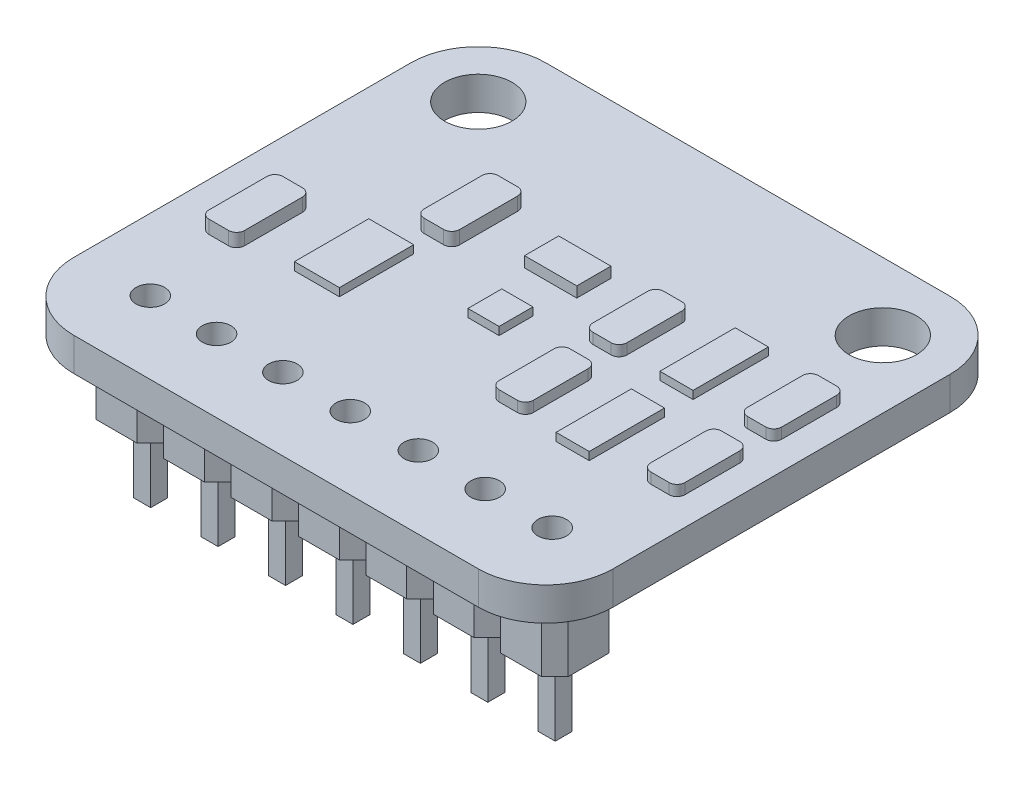
SolidWorks part; units mm, degrees
ref_plane "Front Plane" through (0, 0, 0) normal (0, 0, 1) x (1, 0, 0)
ref_plane "Top Plane" through (0, 0, 0) normal (0, 1, 0) x (1, 0, 0)
ref_plane "Right Plane" through (0, 0, 0) normal (1, 0, 0) x (0, 0, -1)
sketch "Sketch1" plane through (0, 0, 0) normal (0, 1, 0) x (1, 0, 0)
  line L0 (68.1796, -39.0616) -> (124.8504, -39.0616) construction
  line L1 (-9.3411, 12.1911) -> (5.8989, 12.1911)
  line L2 (-11.8811, 9.6511) -> (-11.8811, -3.0489)
  line L3 (-9.3411, -5.5889) -> (5.8989, -5.5889)
  line L4 (8.4389, 9.6511) -> (8.4389, -3.0489)
  line L5 (6.4112, -2.8555) -> (-9.7253, -2.8555) construction
  line L6 (-6.0638, 7.1149) -> (-5.3229, 7.1149)
  line L7 (-10.0841, 3.0308) -> (-9.3432, 3.0308)
  line L8 (-10.3841, 2.7308) -> (-10.3841, 0.547)
  line L9 (-10.0841, 0.247) -> (-9.3432, 0.247)
  line L10 (-9.0432, 2.7308) -> (-9.0432, 0.547)
  line L11 (-7.2867, 3.4702) -> (-5.5917, 3.4702)
  line L12 (-7.2867, 3.4702) -> (-7.2867, 0.6697)
  line L13 (-7.2867, 0.6697) -> (-5.5917, 0.6697)
  line L14 (-5.5917, 3.4702) -> (-5.5917, 0.6697)
  line L15 (-6.3638, 6.8149) -> (-6.3638, 4.6311)
  line L16 (-6.0638, 4.3311) -> (-5.3229, 4.3311)
  line L17 (-5.0229, 6.8149) -> (-5.0229, 4.6311)
  line L18 (6.3874, 3.0901) -> (7.0743, 3.0901)
  line L19 (-3.0469, 6.3858) -> (-1.0787, 6.3858)
  line L20 (-3.0469, 6.3858) -> (-3.0469, 5.0989)
  line L21 (-3.0469, 5.0989) -> (-1.0787, 5.0989)
  line L22 (-1.0787, 6.3858) -> (-1.0787, 5.0989)
  line L23 (0.8488, 2.9162) -> (1.5357, 2.9162)
  line L24 (0.5488, 2.6162) -> (0.5488, 0.547)
  line L25 (0.8488, 0.247) -> (1.5357, 0.247)
  line L26 (1.8357, 2.6162) -> (1.8357, 0.547)
  line L27 (6.0874, 2.7901) -> (6.0874, 0.7209)
  line L28 (6.3874, 0.4209) -> (7.0743, 0.4209)
  line L29 (7.3743, 2.7901) -> (7.3743, 0.7209)
  line L30 (6.4, 6.7237) -> (7.0869, 6.7237)
  line L31 (6.1, 6.4237) -> (6.1, 4.3544)
  line L32 (6.4, 4.0544) -> (7.0869, 4.0544)
  line L33 (7.3869, 6.4237) -> (7.3869, 4.3544)
  line L34 (0.7353, 6.5597) -> (1.4221, 6.5597)
  line L35 (0.4353, 6.2597) -> (0.4353, 4.1904)
  line L36 (0.7353, 3.8904) -> (1.4221, 3.8904)
  line L37 (1.7221, 6.2597) -> (1.7221, 4.1904)
  line L38 (3.2109, 2.8658) -> (4.4599, 2.8658)
  line L39 (3.173, 6.8149) -> (4.422, 6.8149)
  line L40 (3.173, 6.8149) -> (3.173, 3.9783)
  line L41 (3.173, 3.9783) -> (4.422, 3.9783)
  line L42 (4.422, 6.8149) -> (4.422, 3.9783)
  line L47 (-2.4918, 3.6858) -> (-1.3184, 3.6858)
  line L48 (-2.4918, 3.6858) -> (-2.4918, 2.4116)
  line L49 (-2.4918, 2.4116) -> (-1.3184, 2.4116)
  line L50 (-1.3184, 3.6858) -> (-1.3184, 2.4116)
  line L51 (3.2109, 2.8658) -> (3.2109, 0.0292)
  line L52 (3.2109, 0.0292) -> (4.4599, 0.0292)
  line L53 (4.4599, 2.8658) -> (4.4599, 0.0292)
  arc A0 (-11.8811, -3.0489) -> (-9.3411, -5.5889) centre (-9.3411, -3.0489) ccw
  arc A1 (5.8989, -5.5889) -> (8.4389, -3.0489) centre (5.8989, -3.0489) ccw
  arc A2 (5.8989, 12.1911) -> (8.4389, 9.6511) centre (5.8989, 9.6511) cw
  arc A3 (-9.3411, 12.1911) -> (-11.8811, 9.6511) centre (-9.3411, 9.6511) ccw
  circle A4 centre (-9.3411, 9.6511) radius 1.27
  circle A5 centre (5.8989, 9.6511) radius 1.27
  circle A7 centre (-6.6941, -2.8555) radius 0.54
  circle A8 centre (-4.1979, -2.8555) radius 0.54
  circle A9 centre (-1.657, -2.8555) radius 0.54
  circle A10 centre (0.9061, -2.8555) radius 0.54
  circle A11 centre (3.4246, -2.8555) radius 0.54
  circle A12 centre (5.9492, -2.8555) radius 0.54
  circle A13 centre (-9.1904, -2.8555) radius 0.54
  arc A14 (-10.3841, 0.547) -> (-10.0841, 0.247) centre (-10.0841, 0.547) ccw
  arc A15 (-9.3432, 0.247) -> (-9.0432, 0.547) centre (-9.3432, 0.547) ccw
  arc A16 (-9.3432, 3.0308) -> (-9.0432, 2.7308) centre (-9.3432, 2.7308) cw
  arc A17 (-10.0841, 3.0308) -> (-10.3841, 2.7308) centre (-10.0841, 2.7308) ccw
  arc A18 (-6.3638, 4.6311) -> (-6.0638, 4.3311) centre (-6.0638, 4.6311) ccw
  arc A19 (-5.3229, 4.3311) -> (-5.0229, 4.6311) centre (-5.3229, 4.6311) ccw
  arc A20 (-5.3229, 7.1149) -> (-5.0229, 6.8149) centre (-5.3229, 6.8149) cw
  arc A21 (-6.0638, 7.1149) -> (-6.3638, 6.8149) centre (-6.0638, 6.8149) ccw
  arc A22 (1.5357, 0.247) -> (1.8357, 0.547) centre (1.5357, 0.547) ccw
  arc A23 (0.5488, 0.547) -> (0.8488, 0.247) centre (0.8488, 0.547) ccw
  arc A24 (0.8488, 2.9162) -> (0.5488, 2.6162) centre (0.8488, 2.6162) ccw
  arc A25 (1.5357, 2.9162) -> (1.8357, 2.6162) centre (1.5357, 2.6162) cw
  arc A26 (7.0743, 0.4209) -> (7.3743, 0.7209) centre (7.0743, 0.7209) ccw
  arc A27 (6.0874, 0.7209) -> (6.3874, 0.4209) centre (6.3874, 0.7209) ccw
  arc A28 (6.3874, 3.0901) -> (6.0874, 2.7901) centre (6.3874, 2.7901) ccw
  arc A29 (7.0743, 3.0901) -> (7.3743, 2.7901) centre (7.0743, 2.7901) cw
  arc A30 (7.0869, 4.0544) -> (7.3869, 4.3544) centre (7.0869, 4.3544) ccw
  arc A31 (6.1, 4.3544) -> (6.4, 4.0544) centre (6.4, 4.3544) ccw
  arc A32 (6.4, 6.7237) -> (6.1, 6.4237) centre (6.4, 6.4237) ccw
  arc A33 (7.0869, 6.7237) -> (7.3869, 6.4237) centre (7.0869, 6.4237) cw
  arc A34 (1.4221, 3.8904) -> (1.7221, 4.1904) centre (1.4221, 4.1904) ccw
  arc A35 (0.4353, 4.1904) -> (0.7353, 3.8904) centre (0.7353, 4.1904) ccw
  arc A36 (0.7353, 6.5597) -> (0.4353, 6.2597) centre (0.7353, 6.2597) ccw
  arc A37 (1.4221, 6.5597) -> (1.7221, 6.2597) centre (1.4221, 6.2597) cw
  point P8 (-11.8811, -5.5889)
  point P11 (8.4389, -5.5889)
  point P16 (-11.8811, 12.1911)
  point P127 (0, 0)
  point P128 (0, 0)
  point P129 (0, 0)
  dimension "D3" = 2.54
  dimension "D4" = 2.54
  dimension "D5" = 2.54
  dimension "D6" = 1.08
  dimension "D7" = 0.3
  dimension "D8" = 0.3
  dimension "D1" = 20.32
  dimension "D2" = 17.78
extrude "Boss-Extrude1" add sketch "Sketch1" along normal blind 1.25 contours L4 A1 L3 A0 L2 A3 L1 A2 | A4 | A5 | A7 | A8 | A9 | A10 | A11 | A13 | A12
extrude "Boss-Extrude2" add sketch "Sketch1<4>" along normal offset from surface (1.75 mm away) 0.5 contours L10 A15 L9 A14 L8 A17 L7 A16 | L15 A18 L16 A19 L17 A20 L6 A21 up to face at (-1.7211, 1.25, -3.3011) offset beyond the face yes
sketch "Sketch1<4>" plane through (0, 0, 0) normal (0, 1, 0) x (1, 0, 0) same geometry as "Sketch1"
extrude "Boss-Extrude3" add sketch "Sketch1<5>" along normal offset from surface (1.65 mm away) 0.4 contours L24 A23 L25 A22 L26 A25 L23 A24 | L21 L22 L19 L20 | L27 A27 L28 A26 L29 A29 L18 A28 | L31 A31 L32 A30 L33 A33 L30 A32 | L35 A35 L36 A34 L37 A37 L34 A36 up to face at (5.9492, 1.25, 3.3955) offset beyond the face yes
sketch "Sketch1<5>" plane through (0, 0, 0) normal (0, 1, 0) x (1, 0, 0) same geometry as "Sketch1"
extrude "Boss-Extrude4" add sketch "Sketch1<6>" along normal offset from surface (1.55 mm away) 0.3 contours L12 L13 L14 L11 | L40 L41 L42 L39 | L51 L52 L53 L38 | L48 L49 L50 L47 up to face at (6.7435, 1.25, -5.3891) offset beyond the face yes
sketch "Sketch1<6>" plane through (0, 0, 0) normal (0, 1, 0) x (1, 0, 0) same geometry as "Sketch1"
sketch "Sketch2" plane through (0, 0, 0) normal (0, -1, 0) x (1, 0, 0)
  line L0 (6.4112, 2.8555) -> (-9.7253, 2.8555) construction
  line L1 (-10.4604, 4.1255) -> (-7.9204, 4.1255)
  line L2 (-10.4604, 4.1255) -> (-10.4604, 1.5855)
  line L3 (-10.4604, 1.5855) -> (-7.9204, 1.5855)
  line L4 (-7.9204, 4.1255) -> (-7.9204, 1.5855)
  point P4 (-9.1904, 4.1255)
  point P5 (-10.4604, 2.8555)
  dimension "D1" = 2.54
  dimension "D2" = 2.54
extrude "Boss-Extrude5" add sketch "Sketch2" along normal blind 2.54 separate body contours L2 L1 L4 L3
chamfer "Chamfer1" distance 0.5 angle 45 4 edges at (-10.4604, -1.27, 1.5855) (-10.4604, -1.27, 4.1255) (-7.9204, -1.27, 4.1255) (-7.9204, -1.27, 1.5855)
sketch "Sketch3" plane through (0, -2.54, 0) normal (0, -1, 0) x (1, 0, 0)
  line L0 (6.4112, 2.8555) -> (-9.7253, 2.8555) construction
  line L1 (-9.4967, 3.1755) -> (-8.8567, 3.1755)
  line L2 (-9.4967, 3.1755) -> (-9.4967, 2.5355)
  line L3 (-9.4967, 2.5355) -> (-8.8567, 2.5355)
  line L4 (-8.8567, 3.1755) -> (-8.8567, 2.5355)
  point P4 (-9.4967, 2.8555)
  dimension "D1" = 0.64
  dimension "D2" = 0.64
extrude "Boss-Extrude6" add sketch "Sketch3" along normal blind 3
chamfer "Chamfer2" distance 0.2 angle 45 4 edges at (-9.1767, -5.54, 3.1755) (-8.8567, -5.54, 2.8555) (-9.1767, -5.54, 2.5355) (-9.4967, -5.54, 2.8555)
pattern_linear "LPattern1" count 7 spacing 2.54 along (1, 0, 0) of bodies 112 105
